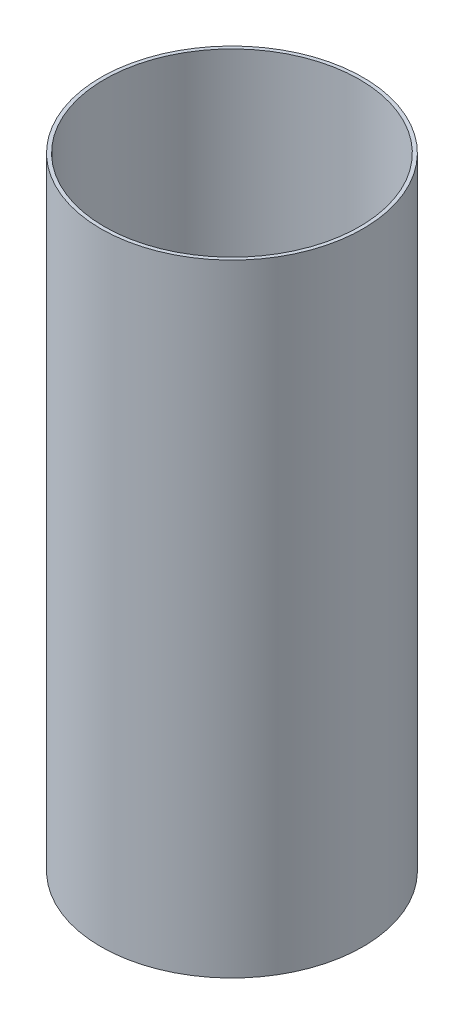
SolidWorks part; units mm, degrees
material "Hexcel AS4C (3000 Filaments)"
ref_plane "Front Plane" through (0, 0, 0) normal (0, 0, 1) x (1, 0, 0)
ref_plane "Top Plane" through (0, 0, 0) normal (0, 1, 0) x (1, 0, 0)
ref_plane "Right Plane" through (0, 0, 0) normal (1, 0, 0) x (0, 0, -1)
sketch "Sketch1" plane through (0, 0, 0) normal (0, 1, 0) x (1, 0, 0)
  circle A0 centre (0, 0) radius 76.454
  circle A1 centre (0, 0) radius 78.5876
  dimension "D1" = 152.908
  dimension "D2" = 157.1752
extrude "Boss-Extrude1" add sketch "Sketch1" along normal blind 372.618
